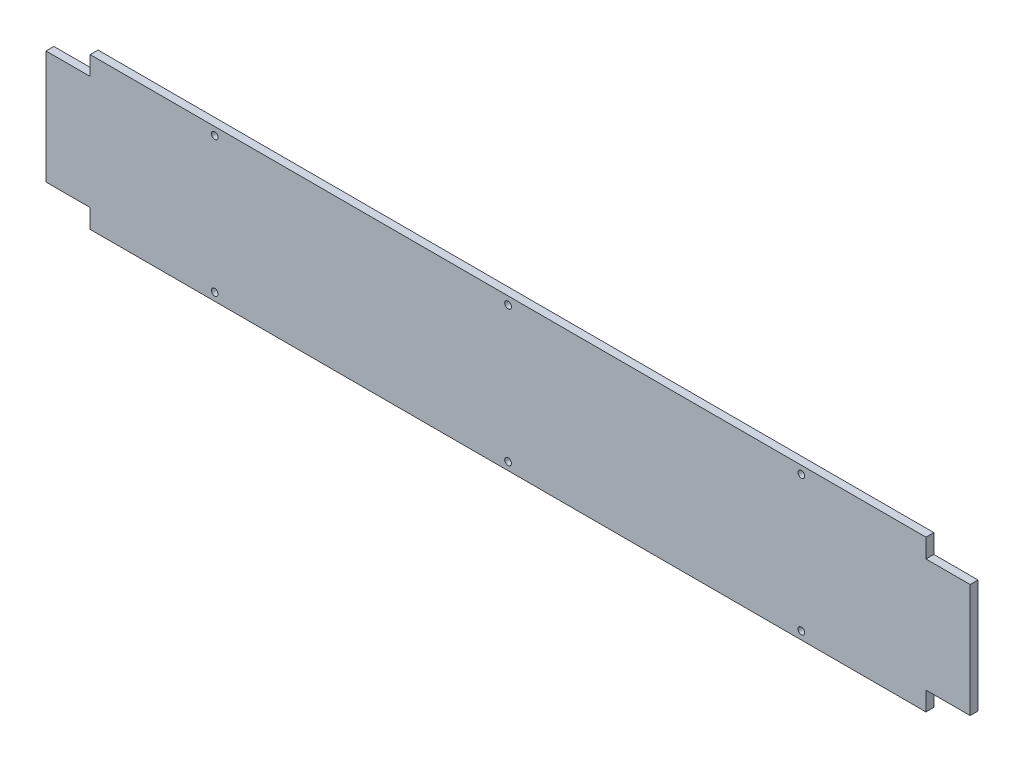
SolidWorks part; units mm, degrees
ref_plane "Front Plane" through (0, 0, 0) normal (0, 0, 1) x (1, 0, 0)
ref_plane "Top Plane" through (0, 0, 0) normal (0, 1, 0) x (1, 0, 0)
ref_plane "Right Plane" through (0, 0, 0) normal (1, 0, 0) x (0, 0, -1)
sketch "Sketch1" plane through (0, 0, 0) normal (0, 0, 1) x (1, 0, 0)
  line L9 (0, 0) -> (530, 0)
  line L10 (0, 0) -> (0, 96)
  line L11 (0, 96) -> (530, 96)
  line L12 (530, 0) -> (530, 96)
  dimension "D1" = 96
  dimension "D2" = 530
extrude "Boss-Extrude1" add sketch "Sketch1" along normal blind 5
sketch "Sketch2" plane through (0, 0, 5) normal (0, 0, 1) x (1, 0, 0)
  line L0 (0, 96) -> (0, 0) construction
  line L3 (530, 96) -> (0, 96) construction
  line L4 (32.0519, 48) -> (507.2554, 48) construction
  circle A0 centre (79, 91) radius 2.125
  circle A1 centre (265, 91) radius 2.125
  circle A2 centre (451, 91) radius 2.125
  circle A3 centre (451, 5) radius 2.125
  circle A4 centre (265, 5) radius 2.125
  circle A5 centre (79, 5) radius 2.125
  dimension "D1" = 4.25
  dimension "D2" = 4.25
  dimension "D3" = 4.25
  dimension "D6" = 186
  dimension "D4" = 79
  dimension "D5" = 186
  dimension "D7" = 5
  dimension "D8" = 48
extrude "Cut-Extrude1" cut sketch "Sketch2" against normal blind 5
sketch "Sketch3" plane through (0, 0, 5) normal (0, 0, 1) x (1, 0, 0)
  line L0 (530, 0) -> (530, 96) construction
  line L1 (530, 84) -> (558, 84)
  line L2 (530, 84) -> (530, 12)
  line L3 (530, 12) -> (558, 12)
  line L4 (558, 84) -> (558, 12)
  line L5 (0, 96) -> (0, 0) construction
  line L6 (0, 84) -> (-28, 84)
  line L7 (0, 84) -> (0, 12)
  line L8 (0, 12) -> (-28, 12)
  line L9 (-28, 84) -> (-28, 12)
  line L10 (530, 96) -> (0, 96) construction
  line L11 (0, 0) -> (530, 0) construction
  dimension "D1" = 12
  dimension "D2" = 28
  dimension "D3" = 12
  dimension "D4" = 12
  dimension "D5" = 12
  dimension "D6" = 28
extrude "Boss-Extrude2" add sketch "Sketch3" against normal blind 5
